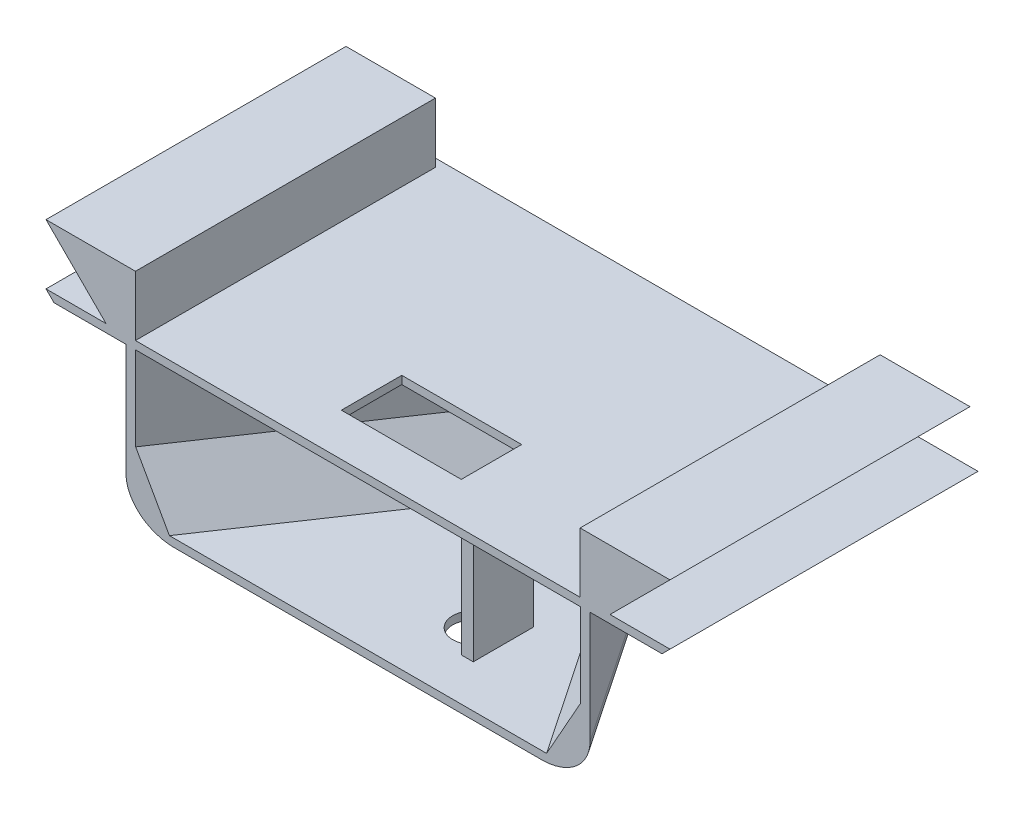
SolidWorks part; units mm, degrees
other "Camera1"
ref_plane "Front Plane" through (0, 0, 0) normal (0, 0, 1) x (1, 0, 0)
ref_plane "Top Plane" through (0, 0, 0) normal (0, 1, 0) x (1, 0, 0)
ref_plane "Right Plane" through (0, 0, 0) normal (1, 0, 0) x (0, 0, -1)
sketch "Sketch1" plane through (0, 0, 0) normal (0, 1, 0) x (1, 0, 0)
  line L0 (0, 0) -> (-116, 0)
  line L1 (-116, 0) -> (-75.5008, 60)
  line L2 (-75.5008, 60) -> (-40.5008, 60)
  line L3 (-40.5008, 60) -> (0, 0)
  dimension "D1" = 60
  dimension "D2" = 116
  dimension "D3" = 35
  dimension "D5" = 72.39
  dimension "D6" = 72.3891
extrude "Boss-Extrude1" add sketch "Sketch1" against normal blind 40
shell "Shell1" thickness 2
chamfer "Chamfer3" distance 15 angle 25 2 edges at (-94.0124, -38, -29) (-21.9884, -38, -29)
fillet "Fillet1" radius 10 2 edges at (-20.2504, -40, -30) (-95.7504, -40, -30)
fillet "Fillet2" radius 5 5 edges at (-40.5008, -15, -60) (-44.0345, -37.0711, -60) (-75.5008, -15, -60) (-71.9671, -37.0711, -60) (-58.0008, -40, -60)
sketch "Sketch12" plane through (0, -40, 0) normal (0, -1, 0) x (-1, 0, 0)
  circle A0 centre (47.2011, 18.0841) radius 5.2
sketch "Sketch13" plane through (0, -2, 0) normal (0, -1, 0) x (1, 0, 0)
  line L1 (-39.8423, -25.7584) -> (-42.8423, -25.7584)
  line L2 (-39.8423, -25.7584) -> (-39.8423, -10.6584)
  line L3 (-39.8423, -10.6584) -> (-42.8423, -10.6584)
  line L4 (-42.8423, -25.7584) -> (-42.8423, -10.6584)
  dimension "D1" = 3
extrude "Boss-Extrude3" add sketch "Sketch13" along normal blind 36
extrude "Cut-Extrude12" cut sketch "Sketch12" against normal blind 9
sketch "Sketch15" plane through (0, 0, 0) normal (0, 1, 0) x (1, 0, 0)
  line L8 (-136, 75) -> (20, 75)
  line L9 (20, 0) -> (20, 75)
  line L10 (20, 0) -> (-136, 0)
  line L11 (-136, 0) -> (-136, 75)
extrude "Boss-Extrude7" add sketch "Sketch15" along normal blind 15
sketch "Sketch16" plane through (0, 0, 0) normal (0, 0, 1) x (1, 0, 0)
  line L8 (20, 15) -> (20, 0)
  line L9 (20, 0) -> (5, 0)
  line L10 (0, 0) -> (20, 0) construction
  line L11 (5, 0) -> (20, 15)
extrude "Cut-Extrude14" cut sketch "Sketch16" against normal blind 75
sketch "Sketch17" plane through (0, 0, 0) normal (0, 0, 1) x (1, 0, 0)
  line L0 (-136, 15) -> (-136, 0)
  line L1 (-136, 0) -> (-121, 0)
  line L2 (-136, 0) -> (-116, 0) construction
  line L3 (-121, 0) -> (-136, 15)
  dimension "D1" = 15
extrude "Cut-Extrude15" cut sketch "Sketch17" against normal blind 75
sketch "Sketch18" plane through (0, 0, 0) normal (0, -1, 0) x (1, 0, 0)
  line L0 (-116, 0) -> (-121, 0)
  line L1 (-121, 0) -> (-136.0045, 0)
  line L2 (-136.0045, 0) -> (-136.0045, -75)
  line L5 (20.0045, -75) -> (20.0045, 0)
  line L6 (20.0045, 0) -> (-116, 0)
  line L9 (-136.0045, -75) -> (-136.0045, -77)
  line L10 (20.0045, -75) -> (20.0045, -77)
  line L13 (-136.0045, -77) -> (20.0045, -77)
extrude "Boss-Extrude8" add sketch "Sketch18" along normal blind 2 contours L5 L6 L0 L1 L2 L9 L13 L10
sketch "Sketch20" plane through (0, -2, 0) normal (0, -1, 0) x (-1, 0, 0)
  line L1 (42.8423, 25.7584) -> (72.8207, 25.7584)
  line L2 (42.8423, 25.7584) -> (42.8423, 10.6584)
  line L3 (42.8423, 10.6584) -> (72.8207, 10.6584)
  line L4 (72.8207, 25.7584) -> (72.8207, 10.6584)
extrude "Cut-Extrude17" cut sketch "Sketch20" against normal blind 39 contours L2 L1 L4 L3
sketch "Sketch26" plane through (-42.8423, 0, 0) normal (-1, 0, 0) x (0, 0, 1)
  line L6 (-10.6584, -38) -> (-18.2084, -38)
  line L7 (-10.6584, -38) -> (-10.6584, -10.7935)
  line L8 (-10.6584, -10.7935) -> (-18.2084, -10.7935)
  line L9 (-18.2084, -38) -> (-18.2084, -10.7935)
sketch "Sketch29" plane through (-42.8423, 0, 0) normal (-1, 0, 0) x (0, 0, 1)
  circle A0 centre (-18.2084, -10.7935) radius 2.1
extrude "Cut-Extrude22" cut sketch "Sketch29" against normal blind 10 contours A0
sketch "Sketch32" plane through (0, 0, -58) normal (0, 0, 1) x (1, 0, 0)
sketch "Sketch33" plane through (0, 0, -58) normal (0, 0, 1) x (1, 0, 0)
sketch "Sketch34" plane through (0, 0, -58) normal (0, 0, 1) x (1, 0, 0)
  line L0 (-74.4378, -23) -> (-74.4378, -2) construction
  line L1 (-53.7528, -23.65) -> (-62.2528, -23.65)
  line L2 (-53.7528, -23.65) -> (-53.7528, -15.15)
  line L3 (-53.7528, -15.15) -> (-62.2528, -15.15)
  line L4 (-62.2528, -23.65) -> (-62.2528, -15.15)
  line L10 (-41.5637, -2) -> (-74.4378, -2) construction
  circle A0 centre (-68.5028, -19.5) radius 1.1
  circle A1 centre (-68.5028, -7) radius 1.1
  dimension "D5" = 6.25
  dimension "D6" = 17.5
  dimension "D7" = 6.25
  dimension "D8" = 5
  dimension "D1" = 12.185
  dimension "D2" = 8.5
  dimension "D3" = 8.5
  dimension "D4" = 13.15
extrude "Cut-Extrude23" cut sketch "Sketch34" against normal blind 10
sketch "Sketch35" plane through (0, 0, -58) normal (0, 0, 1) x (1, 0, 0)
  line L0 (-53.7528, -23.65) -> (-53.7528, -15.15) construction
  line L1 (-41.5637, -2) -> (-74.4378, -2) construction
  circle A0 centre (-47.5028, -19.5) radius 1.1
  circle A1 centre (-47.5028, -7) radius 1.1
  dimension "D1" = 6.25
  dimension "D2" = 17.5
  dimension "D3" = 6.25
  dimension "D4" = 5
extrude "Cut-Extrude24" cut sketch "Sketch35" against normal blind 10
sketch "Sketch36" plane through (0, 0, 0) normal (0, 0, 1) x (1, 0, 0)
  line L0 (-136, 15) -> (20, 15) construction
  line L1 (-2.4692, 15) -> (-113.6392, 15)
  line L2 (-2.4692, 15) -> (-2.4692, 0)
  line L3 (-2.4692, 0) -> (-113.6392, 0)
  line L4 (-113.6392, 15) -> (-113.6392, 0)
extrude "Cut-Extrude25" cut sketch "Sketch36" against normal blind 85 contours L2 L1 L4 L3
chamfer "Chamfer4" distance 2 angle 45 3 edges at (20.0045, -2, -38.5) (-58, -2, -77) (-136.0045, -2, -38.5)
